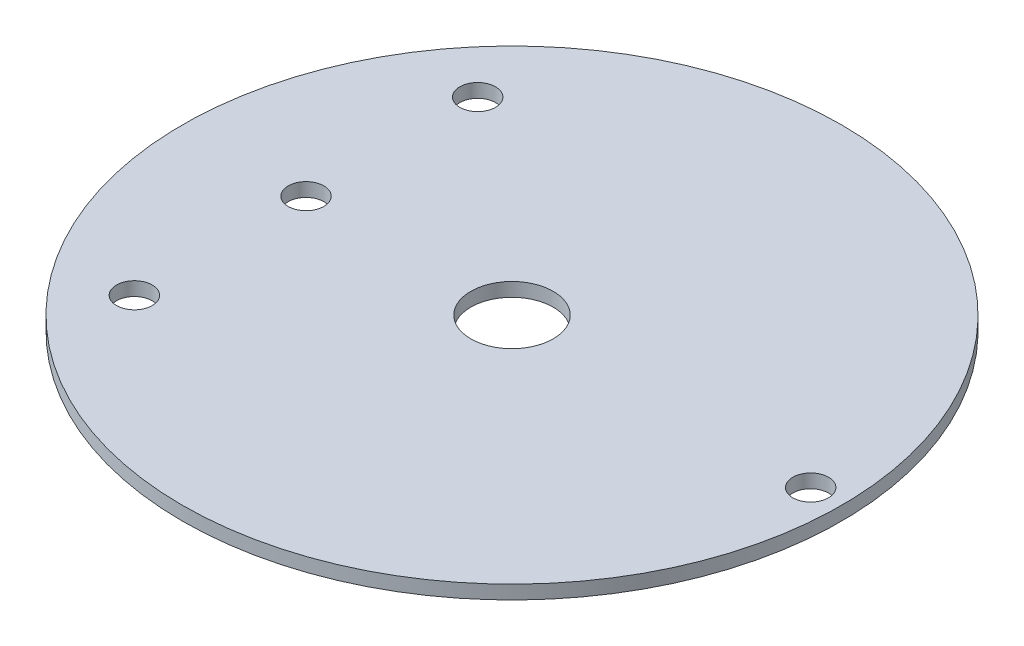
SolidWorks part; units mm, degrees
ref_plane "Front Plane" through (0, 0, 0) normal (0, 0, 1) x (1, 0, 0)
ref_plane "Top Plane" through (0, 0, 0) normal (0, 1, 0) x (1, 0, 0)
ref_plane "Right Plane" through (0, 0, 0) normal (1, 0, 0) x (0, 0, -1)
sketch "Sketch1" plane through (0, 0, 0) normal (0, 1, 0) x (1, 0, 0)
  line L0 (-30, -25) -> (-30, 25) construction
  line L1 (0, 0) -> (43.5, 0) construction
  circle A0 centre (0, 0) radius 48
  circle A1 centre (-30, 0) radius 2.6
  circle A2 centre (0, 0) radius 6
  circle A3 centre (-30, 25) radius 2.6
  circle A4 centre (-30, -25) radius 2.6
  circle A5 centre (43.5, 0) radius 2.6
  point P9 (-30, 0)
  dimension "D1" = 96
  dimension "D2" = 5.2
  dimension "D4" = 12
  dimension "D3" = 30
  dimension "D5" = 50
  dimension "D6" = 43.5
extrude "Boss-Extrude1" add sketch "Sketch1" along normal blind 2
